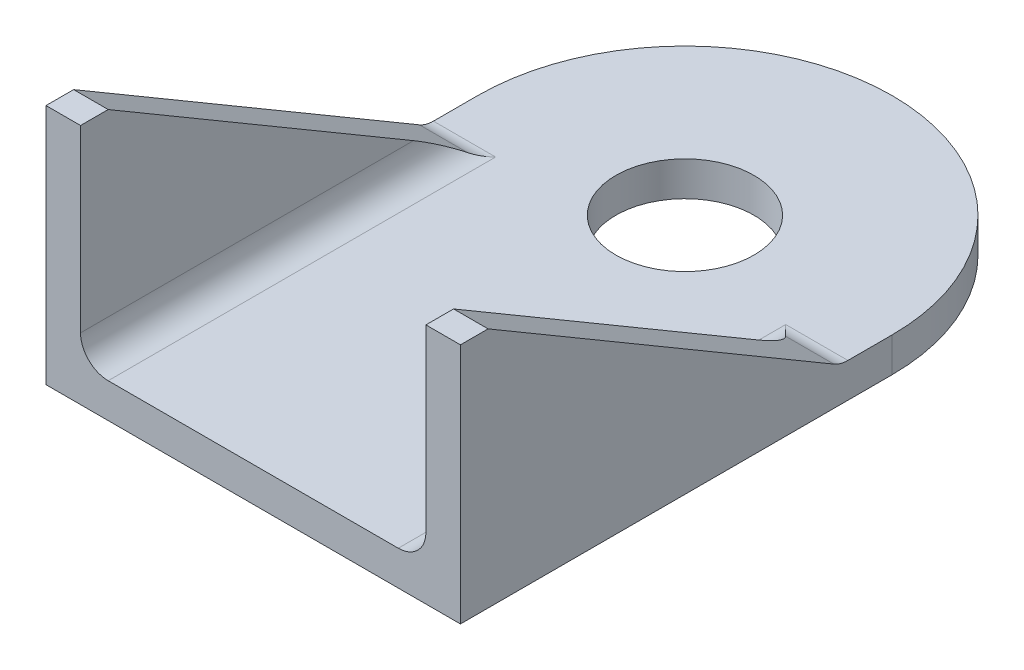
SolidWorks part; units mm, degrees
material "AISI 304"
ref_plane "前视基准面" through (0, 0, 0) normal (0, 0, 1) x (1, 0, 0)
ref_plane "上视基准面" through (0, 0, 0) normal (0, 1, 0) x (1, 0, 0)
ref_plane "右视基准面" through (0, 0, 0) normal (1, 0, 0) x (0, 0, -1)
sketch "草图1" plane through (0, 0, 0) normal (0, 1, 0) x (1, 0, 0)
  line L0 (-12, 0) -> (-12, -25)
  line L1 (-12, -25) -> (12, -25)
  line L2 (12, -25) -> (12, 0)
  circle A0 centre (0, 0) radius 4
  circle A1 centre (0, 0) radius 12
  dimension "D1" = 8
  dimension "D2" = 24
  dimension "D3" = 25
extrude "凸台-拉伸1" add sketch "草图1" along normal blind 2 contours A1 A0 | A1 L0 L1 L2 region at (0, 0, 16.9821) region at (0, 0, -11.6606)
sketch "草图3" plane through (12, 0, 0) normal (1, 0, 0) x (0, 0, -1)
  line L0 (-25, 2) -> (-25, 14)
  line L1 (-25, 14) -> (-23.4, 14)
  line L2 (-23.4, 14) -> (-3, 2)
  line L4 (-25, 2) -> (0, 2) construction
  line L5 (-3, 2) -> (-25, 2)
  dimension "D1" = 1.6
  dimension "D4" = 12
extrude "凸台-拉伸2" add sketch "草图3" against normal blind 2
fillet "圆角1" radius 1.6 2 edges at (10, 2, 14) (11, 2, 3)
mirror "镜向1" about plane through (0, 0, 0) normal (1, 0, 0) of "圆角1", "凸台-拉伸2"
ref_plane "基准面1" through (0, 0, 0) normal (0, 0, 1) x (1, 0, 0)
sketch "草图4" [suppressed] plane through (0, 0, 0) normal (0, 0, 1) x (1, 0, 0)
  circle A0 centre (0, 0) radius 41.9162
sketch "草图7" plane through (0, 0, 0) normal (0, -1, 0) x (1, 0, 0)
  circle A0 centre (0, 0) radius 9
split line "分割线1"
sketch "草图8" plane through (0, 0, 0) normal (0, -1, 0) x (1, 0, 0)
  circle A0 centre (0, 0) radius 12
split line "分割线2"
